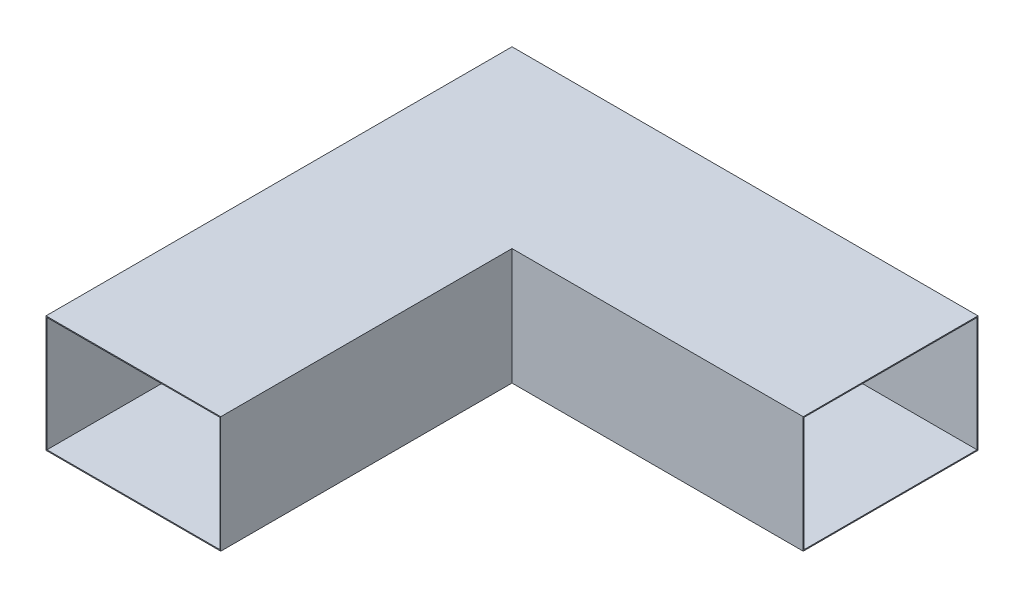
SolidWorks part; units mm, degrees
ref_plane "Front Plane" through (0, 0, 0) normal (0, 0, 1) x (1, 0, 0)
ref_plane "Top Plane" through (0, 0, 0) normal (0, 1, 0) x (1, 0, 0)
ref_plane "Right Plane" through (0, 0, 0) normal (1, 0, 0) x (0, 0, -1)
sketch "Sketch1" plane through (0, 0, 0) normal (0, 1, 0) x (1, 0, 0)
  line L1 (-609.6, 609.6) -> (609.6, 609.6)
  line L2 (-609.6, 609.6) -> (-609.6, -609.6)
  line L3 (-609.6, -609.6) -> (609.6, -609.6)
  line L4 (609.6, 609.6) -> (609.6, -609.6)
  dimension "D1" = 1219.2
  dimension "D2" = 1219.2
  dimension "D3" = 609.6
  dimension "D4" = 609.6
extrude "Boss-Extrude1" add sketch "Sketch1" along normal blind 304.8
sketch "Sketch2" plane through (0, 304.8, 0) normal (0, 1, 0) x (1, 0, 0)
  line L1 (-152.4, 152.4) -> (609.6, 152.4)
  line L2 (-152.4, 152.4) -> (-152.4, -609.6)
  line L3 (-152.4, -609.6) -> (609.6, -609.6)
  line L4 (609.6, 152.4) -> (609.6, -609.6)
  dimension "D1" = 762
extrude "Cut-Extrude1" cut sketch "Sketch2" against normal blind 304.8
shell "Shell1" thickness 2.54 removed face at (609.6, 152.4, -381) removed face at (-381, 152.4, 609.6)
